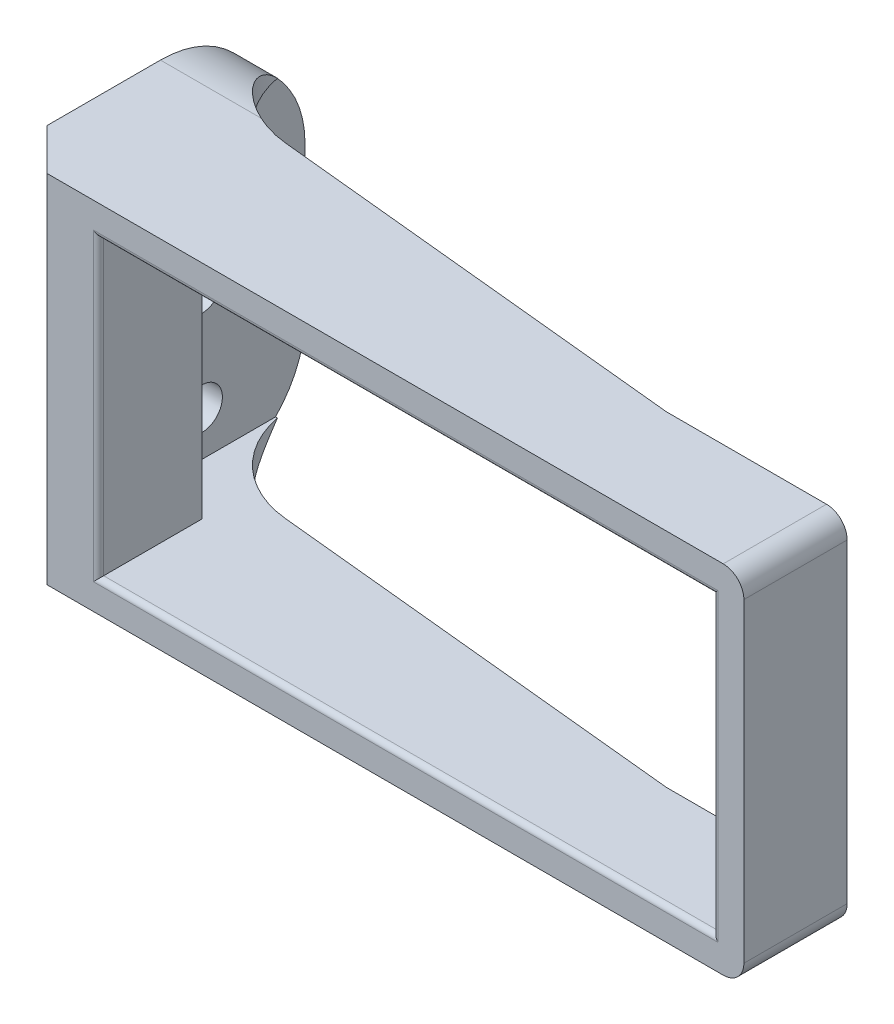
SolidWorks part; units mm, degrees
ref_plane "Front Plane" through (0, 0, 0) normal (0, 0, 1) x (1, 0, 0)
ref_plane "Top Plane" through (0, 0, 0) normal (0, 1, 0) x (1, 0, 0)
ref_plane "Right Plane" through (0, 0, 0) normal (1, 0, 0) x (0, 0, -1)
sketch "Sketch1" plane through (0, 0, 12) normal (0, 0, -1) x (-1, 0, 0)
  line L0 (-56, 0) -> (0, 0) construction
  line L1 (-57.75, 0.5) -> (1.75, 0.5)
  line L2 (-57.75, 0.5) -> (-57.75, -28)
  line L3 (-57.75, -28) -> (1.75, -28)
  line L4 (1.75, 0.5) -> (1.75, -28)
  line L5 (0, -27.5) -> (-56, -27.5) construction
  line L6 (-56, -27.5) -> (-56, 0) construction
  line L7 (0, 0) -> (0, -27.5) construction
  line L9 (-60.75, 3.5) -> (6.75, 3.5)
  line L10 (-60.75, 3.5) -> (-60.75, -31)
  line L11 (-60.75, -31) -> (6.75, -31)
  line L12 (6.75, 3.5) -> (6.75, -31)
  dimension "D1" = 0.5
  dimension "D2" = 0.5
  dimension "D3" = 1.75
  dimension "D4" = 1.75
  dimension "D5" = 3
  dimension "D6" = 3
  dimension "D7" = 3
  dimension "D8" = 5
extrude "Boss-Extrude1" add sketch "Sketch1" along normal blind 10
fillet "Fillet1" radius 2 2 edges at (60.75, -31, 7) (60.75, 3.5, 7)
sketch "Sketch2" plane through (-6.75, 0, 0) normal (-1, 0, 0) x (0, 0, 1)
  line L0 (2, -31) -> (12, -31) construction
  line L1 (12, 3.5) -> (-13, 3.5)
  line L2 (12, 3.5) -> (12, -31)
  line L3 (12, -31) -> (-13, -31)
  line L4 (-13, 3.5) -> (-13, -31)
  line L5 (-3, 3.5) -> (-3, -31) construction
  circle A0 centre (-3, -13.75) radius 2
  circle A1 centre (-3, -3.75) radius 2
  circle A2 centre (-3, -23.75) radius 2
  dimension "D3" = 4
  dimension "D1" = 25
  dimension "D2" = 10
  dimension "D4" = 10
  dimension "D5" = 10
extrude "Boss-Extrude2" add sketch "Sketch2" along normal blind 4
fillet "Fillet2" radius 10 2 edges at (-8.75, -31, -13) (-8.75, 3.5, -13)
ref_plane "Plane1" through (0, -13.75, 0) normal (0, 1, 0) x (1, 0, 0)
sketch "Sketch3" plane through (0, 3.5, 0) normal (0, 1, 0) x (1, 0, 0)
  line L0 (-6.75, 3) -> (43.25, -2)
  line L1 (-6.75, -2) -> (58.75, -2) construction
  line L2 (-6.75, 3) -> (-6.75, -2)
  line L3 (-6.75, -2) -> (43.25, -2)
  dimension "D1" = 50
extrude "Boss-Extrude3" add sketch "Sketch3" against normal blind 3
mirror "Mirror1" about plane through (0, -13.75, 0) normal (0, 1, 0) of "Boss-Extrude3"
chamfer "Chamfer1" distance 4 angle 45 1 edges at (-10.75, -13.75, 12)
fillet "Fillet3" radius 0.5 4 edges at (57.75, -13.75, 12) (28, -28, 12) (28, 0.5, 12) (-1.75, -13.75, 12)
fillet "Fillet4" radius 10 2 edges at (-6.75, 2, -3) (-6.75, -29.5, -3)
